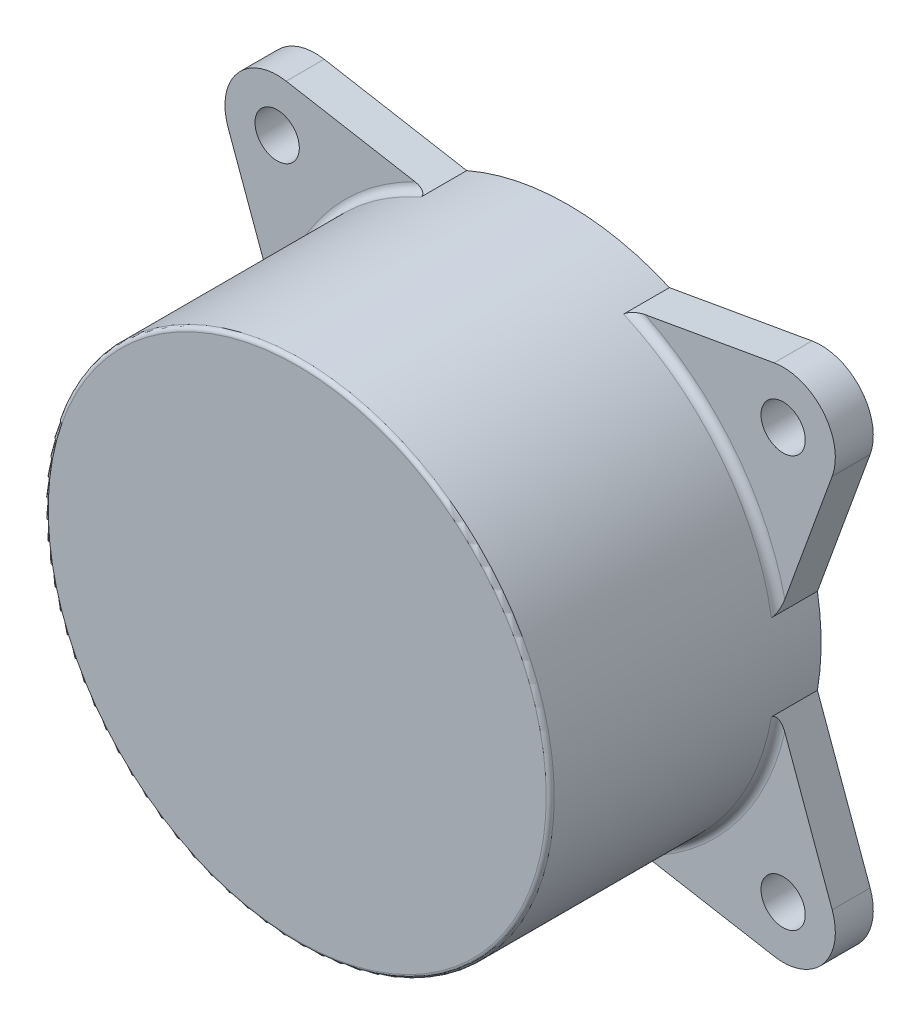
SolidWorks part; units mm, degrees
ref_plane "Front Plane" through (0, 0, 0) normal (0, 0, 1) x (1, 0, 0)
ref_plane "Top Plane" through (0, 0, 0) normal (0, 1, 0) x (1, 0, 0)
ref_plane "Right Plane" through (0, 0, 0) normal (1, 0, 0) x (0, 0, -1)
sketch "Sketch1" plane through (0, 0, 0) normal (0, 0, 1) x (1, 0, 0)
  circle A0 centre (0, 0) radius 40.005
  dimension "D1" = 80.01
extrude "Boss-Extrude1" add sketch "Sketch1" along normal blind 36.83
sketch "Sketch2" plane through (0, 0, 0) normal (0, 0, -1) x (-1, 0, 0)
  line L0 (0, 54.4256) -> (0, -52.4517) construction
  line L1 (16.0254, 36.655) -> (38.5665, 40.6296)
  line L2 (47.7572, 29.6766) -> (39.4254, 6.7852)
  line L3 (0, 0) -> (91.8992, 0) construction
  line L4 (47.7572, -29.6766) -> (39.4254, -6.7852)
  line L5 (16.0254, -36.655) -> (38.5665, -40.6296)
  line L6 (-16.0254, -36.655) -> (-38.5665, -40.6296)
  line L7 (-47.7572, -29.6766) -> (-39.4254, -6.7852)
  line L8 (-47.7572, 29.6766) -> (-39.4254, 6.7852)
  line L9 (-16.0254, 36.655) -> (-38.5665, 40.6296)
  arc A0 (-16.0254, 36.655) -> (16.0254, 36.655) centre (0, 0) cw
  circle A1 centre (0, 0) radius 40.005 construction
  circle A2 centre (40, 32.5) radius 3.5
  arc A3 (38.5665, 40.6296) -> (47.7572, 29.6766) centre (40, 32.5) cw
  arc A4 (39.4254, 6.7852) -> (40.005, 0) centre (0, 0) cw
  arc A5 (38.5665, -40.6296) -> (47.7572, -29.6766) centre (40, -32.5) ccw
  circle A6 centre (40, -32.5) radius 3.5
  arc A7 (-16.0254, -36.655) -> (16.0254, -36.655) centre (0, 0) ccw
  circle A8 centre (-40, -32.5) radius 3.5
  arc A9 (-38.5665, -40.6296) -> (-47.7572, -29.6766) centre (-40, -32.5) cw
  arc A10 (-39.4254, 6.7852) -> (-40.005, 0) centre (0, 0) ccw
  arc A11 (-38.5665, 40.6296) -> (-47.7572, 29.6766) centre (-40, 32.5) ccw
  circle A12 centre (-40, 32.5) radius 3.5
  point P8 (40, 32.5)
  circle M1 centre (0, 0) radius 40.005
  dimension "D3" = 7
  dimension "D6" = 8.255
  dimension "D1" = 40
  dimension "D2" = 32.5
  dimension "D4" = 60
  dimension "D5" = 20
extrude "Boss-Extrude2" add sketch "Sketch2" along normal blind 6 contours L9 A11 L8 A12 M1 | M1 | A3 L1 L2 A2 M1 | A9 L6 L7 A8 M1 | L5 A5 L4 A6 M1 region at (0, 0, 0) region at (-36.3257, 29.1032, 0) region at (36.3257, 29.1032, 0) region at (-36.3257, -29.1032, 0) region at (36.3257, -29.1032, 0)
fillet "Fillet1" radius 0.635 1 edges at (40.005, 0, 36.83)
fillet "Fillet2" radius 1.27 4 edges
